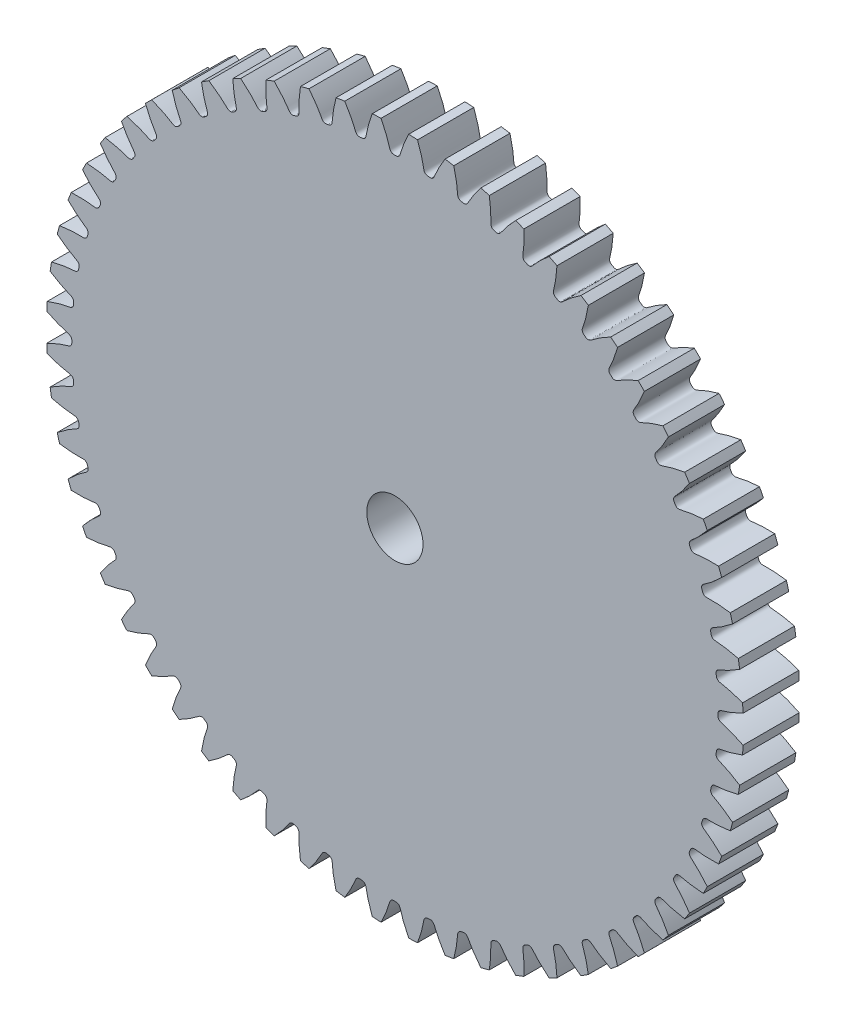
SolidWorks part; units mm, degrees
ref_plane "前视基准面" through (0, 0, 0) normal (0, 0, 1) x (1, 0, 0)
ref_plane "上视基准面" through (0, 0, 0) normal (0, 1, 0) x (1, 0, 0)
ref_plane "右视基准面" through (0, 0, 0) normal (1, 0, 0) x (0, 0, -1)
other "Configuration Table"
ref_axis "基准轴1" through (0, 0, 55) along (0, 0, -1)
sketch "SketchRevolveSpurGear1" plane through (0, 0, 0) normal (1, 0, 0) x (0, 0, -1)
  line L0 (0, 0) -> (1, 0) construction
  line L1 (-5, 0) -> (-5, 62)
  line L2 (-5, 62) -> (5, 62)
  line L3 (5, 62) -> (5, 0)
  line L4 (5, 0) -> (-5, 0)
revolve "SpurGear1" add sketch "SketchRevolveSpurGear1" angle 360 about L0
sketch "SketchToothSpurGear1" plane through (0, 0, 0) normal (0, 0, 1) x (1, 0, 0)
  arc A0 (62.0493, 2.5099) -> (62.0493, -2.5099) centre (0, 0) cw
  spline S0 degree 3 poles (62.0493, -2.5099) (61.8808, -2.4237) (61.6298, -2.2987) (61.2966, -2.1398) (61.055, -2.0279) (60.8186, -1.9215) (60.5875, -1.8206) (60.3617, -1.7251) (60.1414, -1.6347) (59.9267, -1.5495) (59.7176, -1.4691) (59.5142, -1.3936) (59.3166, -1.3227) (59.1248, -1.2563) (58.9391, -1.1943) (58.7593, -1.1364) (58.5856, -1.083) (58.3405, -1.0086) (58.1216, -0.9581) (57.9426, -0.8805) (57.8626, -0.8379) (57.7777, -0.7808) (57.6863, -0.6999) (57.5933, -0.5815) (57.52, -0.4205) (57.4921, -0.218) (57.5043, 0) (57.4921, 0.218) (57.52, 0.4205) (57.5933, 0.5815) (57.6863, 0.6999) (57.7777, 0.7808) (57.8626, 0.8379) (57.9426, 0.8805) (58.1216, 0.9581) (58.3405, 1.0086) (58.5856, 1.083) (58.7593, 1.1364) (58.9391, 1.1943) (59.1248, 1.2563) (59.3166, 1.3227) (59.5142, 1.3936) (59.7176, 1.4691) (59.9267, 1.5495) (60.1414, 1.6347) (60.3617, 1.7251) (60.5875, 1.8206) (60.8186, 1.9215) (61.055, 2.0279) (61.2966, 2.1398) (61.6298, 2.2987) (61.8808, 2.4237) (62.0493, 2.5099) knots 0 0 0 0 0.051766 0.076686 0.100963 0.124598 0.147592 0.169943 0.191651 0.212718 0.233143 0.252925 0.272065 0.290563 0.308419 0.325633 0.342204 0.358133 0.395729 0.403327 0.411415 0.420483 0.431261 0.444675 0.461387 0.478965 0.5 0.521035 0.538613 0.555325 0.568739 0.579517 0.588585 0.596673 0.604271 0.641867 0.657796 0.674367 0.691581 0.709437 0.727935 0.747075 0.766857 0.787282 0.808349 0.830057 0.852408 0.875402 0.899037 0.923314 0.948234 1 1 1 1
extrude "ToothExtrudeCutSpurGear1" cut sketch "SketchToothSpurGear1" against normal blind 5 and the other way blind 5
pattern_circular "PatternSpurGear1" count 60 every 6 about axis through (0, 0, 55) along (0, 0, -1) of "ToothExtrudeCutSpurGear1"
sketch "BoreRevolveSketch" plane through (0, 0, 0) normal (1, 0, 0) x (0, 0, -1)
  line L0 (0, 0) -> (1, 0) construction
  line L1 (-5, 0) -> (5, 0)
  line L2 (5, 0) -> (5, 5)
  line L3 (5, 5) -> (-5, 5)
  line L4 (-5, 5) -> (-5, 0)
  dimension "TaperSide1" = 5
  dimension "TaperSide2" = 5
revolve "BoreRevolveCut" cut sketch "BoreRevolveSketch" angle 360 about L0
sketch "AuxiliarySketchSpurGear1" plane through (0, 0, 0) normal (0, 0, 1) x (1, 0, 0)
  circle A0 centre (0, 0) radius 60 construction
  circle A1 centre (0, 0) radius 56.3816 construction
  circle A2 centre (0, 0) radius 58.183 construction
  circle A3 centre (0, 0) radius 62 construction
  circle A4 centre (0, 0) radius 57.5 construction
  dimension "PitchDiameter" = 120
  dimension "BaseDiameter" = 112.7631
  dimension "FormDiameter" = 116.366
  dimension "MajorDiameter" = 124
  dimension "MinorDiameter" = 115
